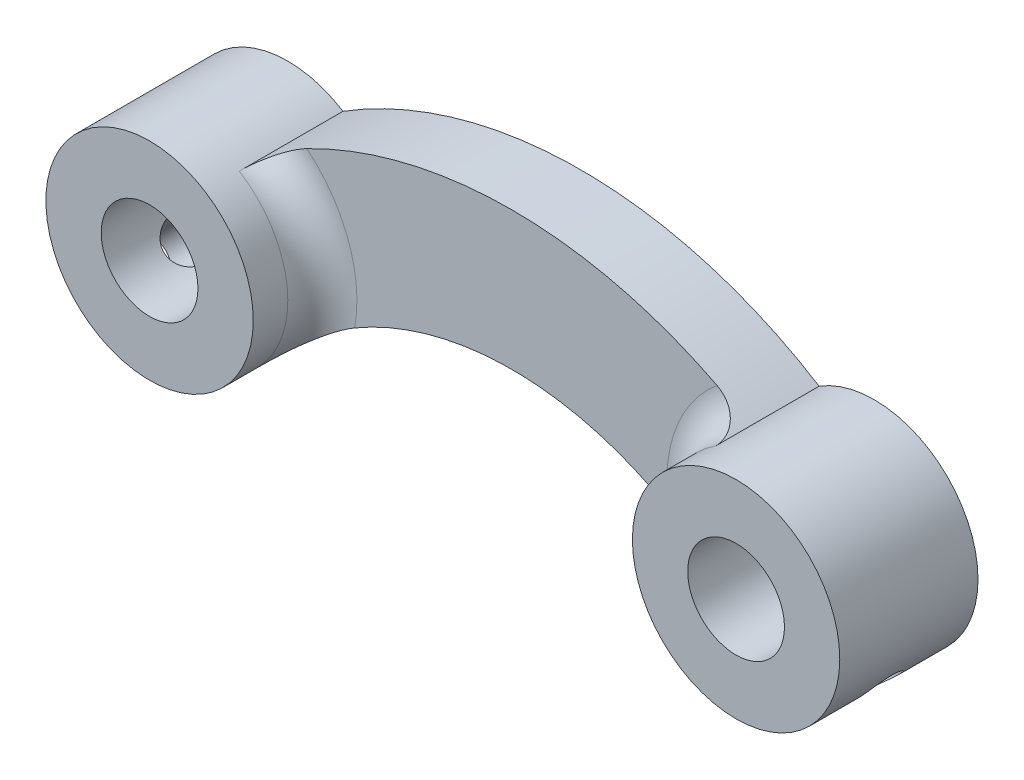
SolidWorks part; units mm, degrees
material "ABS PC"
ref_plane "Front Plane" through (0, 0, 0) normal (0, 0, 1) x (1, 0, 0)
ref_plane "Top Plane" through (0, 0, 0) normal (0, 1, 0) x (1, 0, 0)
ref_plane "Right Plane" through (0, 0, 0) normal (1, 0, 0) x (0, 0, -1)
sketch "Sketch1" plane through (0, 0, 0) normal (0, 0, 1) x (1, 0, 0)
  line L0 (-26.9408, 26.9408) -> (0, 0) construction
  line L1 (0, 0) -> (-51.4114, 0) construction
  line L2 (26.9408, 26.9408) -> (0, 0) construction
  circle A0 centre (0, 0) radius 38.1 construction
  circle A1 centre (-26.9408, 26.9408) radius 4.445
  arc A2 (-21.8707, 35.0043) -> (-20.2056, 20.2056) centre (-26.9408, 26.9408) ccw
  circle A3 centre (26.9408, 26.9408) radius 4.445
  arc A4 (20.2056, 20.2056) -> (21.8707, 35.0043) centre (26.9408, 26.9408) ccw
  arc A6 (21.8707, 35.0043) -> (-21.8707, 35.0043) centre (0, 0) ccw
  arc A7 (20.2056, 20.2056) -> (-20.2056, 20.2056) centre (0, 0) ccw
  dimension "D1" = 76.2
  dimension "D2" = 8.89
  dimension "D4" = 19.05
  dimension "D5" = 8.89
  dimension "D6" = 19.05
  dimension "D7" = 57.15
  dimension "D8" = 82.55
  dimension "D3" = 45
extrude "Boss-Extrude1" add sketch "Sketch1" along normal blind 12.7
sketch "Sketch2" plane through (0, 0, 12.7) normal (0, 0, 1) x (1, 0, 0)
  arc A0 (-20.2056, 20.2056) -> (-21.8707, 35.0043) centre (-26.9408, 26.9408) ccw
  arc A1 (21.8707, 35.0043) -> (20.2056, 20.2056) centre (26.9408, 26.9408) ccw
  arc A2 (21.8707, 35.0043) -> (-21.8707, 35.0043) centre (0, 0) ccw construction
  arc A3 (21.8707, 35.0043) -> (-21.8707, 35.0043) centre (0, 0) ccw
  arc A4 (20.2056, 20.2056) -> (-20.2056, 20.2056) centre (0, 0) ccw construction
  arc A5 (20.2056, 20.2056) -> (-20.2056, 20.2056) centre (0, 0) ccw
extrude "Cut-Extrude1" cut sketch "Sketch2" against normal blind 6.35
fillet "Fillet1" radius 3.175 2 edges at (17.4755, 28.0058, 6.35) (-17.4755, 28.0058, 6.35)
ref_plane "Plane1" through (0, 0, 0) normal (-0.7071, 0.7071, 0) x (0, 0, -1)
sketch "Sketch3" plane through (0, 0, 0) normal (-0.7071, 0.7071, 0) x (0, 0, -1)
  line L2 (-9.525, -38.1) -> (0, -38.1) construction
  line L3 (-12.7, -28.575) -> (-12.7, -47.625) construction
  circle A0 centre (-6.35, -38.1) radius 1.8987
  point P2 (-6.5309, -39.6282)
  point P3 (-7.9844, -39.0737)
  dimension "D1" = 3.7973
  dimension "D2" = 6.35
extrude "Cut-Extrude2" cut sketch "Sketch3" against normal through all
mirror "Mirror1" about plane through (0, 0, 0) normal (1, 0, 0) of "Cut-Extrude2"
